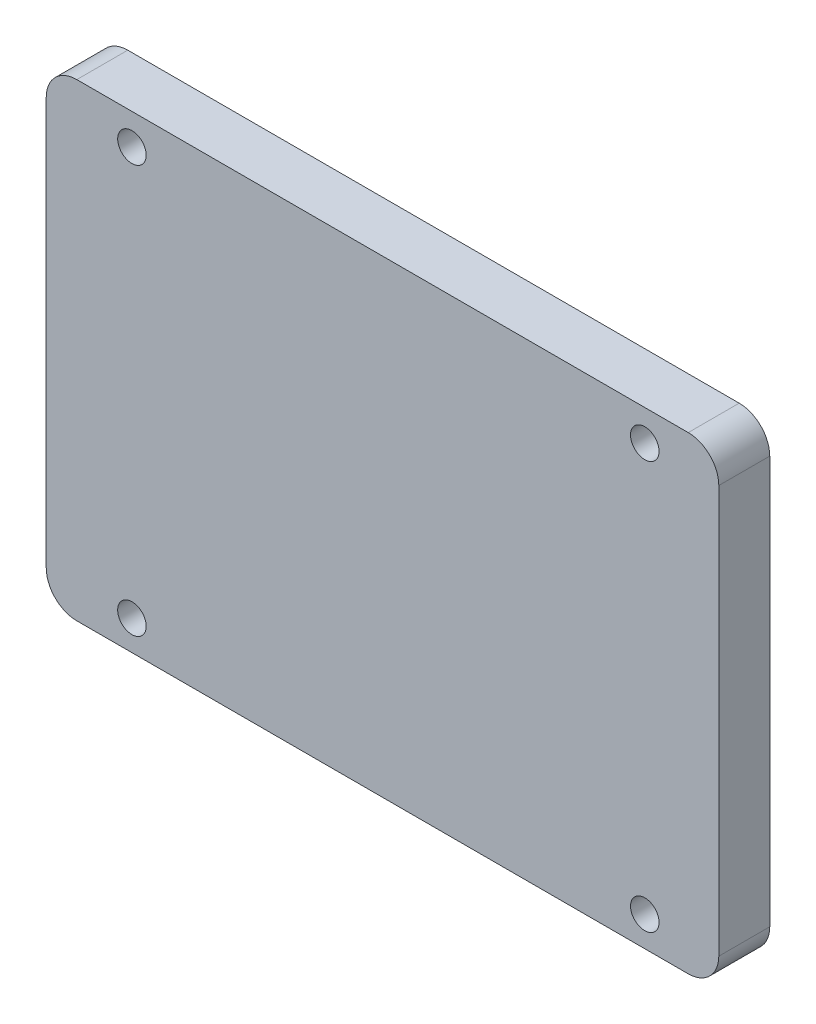
SolidWorks part; units mm, degrees
ref_plane "前视基准面" through (0, 0, 0) normal (0, 0, 1) x (1, 0, 0)
ref_plane "上视基准面" through (0, 0, 0) normal (0, 1, 0) x (1, 0, 0)
ref_plane "右视基准面" through (0, 0, 0) normal (1, 0, 0) x (0, 0, -1)
other "Configuration Table"
sketch "草图2" plane through (0, 0, 0) normal (0, 0, 1) x (1, 0, 0)
  line L1 (15, 0) -> (315, 0)
  line L2 (0, 15) -> (0, 215)
  line L3 (15, 230) -> (315, 230)
  line L4 (330, 15) -> (330, 215)
  arc A0 (15, 0) -> (0, 15) centre (15, 15) cw
  arc A1 (315, 0) -> (330, 15) centre (315, 15) ccw
  arc A2 (315, 230) -> (330, 215) centre (315, 215) cw
  arc A3 (0, 215) -> (15, 230) centre (15, 215) cw
  point P7 (0, 0)
  point P10 (330, 0)
  point P15 (0, 230)
  dimension "D3" = 15
  dimension "D1" = 230
  dimension "D2" = 330
extrude "凸台-拉伸1" add sketch "草图2" along normal blind 25
sketch "草图4" plane through (0, 0, 25) normal (0, 0, 1) x (1, 0, 0)
  line L1 (6.9548, 222.6692) -> (321.9548, 222.6692)
  line L2 (6.9548, 222.6692) -> (6.9548, 7.6692)
  line L3 (6.9548, 7.6692) -> (321.9548, 7.6692)
  line L4 (321.9548, 222.6692) -> (321.9548, 7.6692)
  line L5 (24.7811, 206.8156) -> (304.7811, 206.8156)
  line L6 (24.7811, 206.8156) -> (24.7811, 21.8156)
  line L7 (24.7811, 21.8156) -> (304.7811, 21.8156)
  line L8 (304.7811, 206.8156) -> (304.7811, 21.8156)
  circle A0 centre (42.0495, 214.8391) radius 7
  circle A1 centre (293.6848, 214.8391) radius 7
  circle A2 centre (293.6848, 14.6692) radius 7
  circle A3 centre (42.0495, 14.6692) radius 7
  dimension "D1" = 315
  dimension "D2" = 215
  dimension "D3" = 185
  dimension "D4" = 280
extrude "切除-拉伸5" cut sketch "草图4" against normal up to surface (25 mm away) contours A1 | A2 | A3 | A0 region at (42.0495, 14.6692, 25) region at (293.6848, 14.6692, 25) region at (293.6848, 214.8391, 25) up to face at (165, 115, 0)
